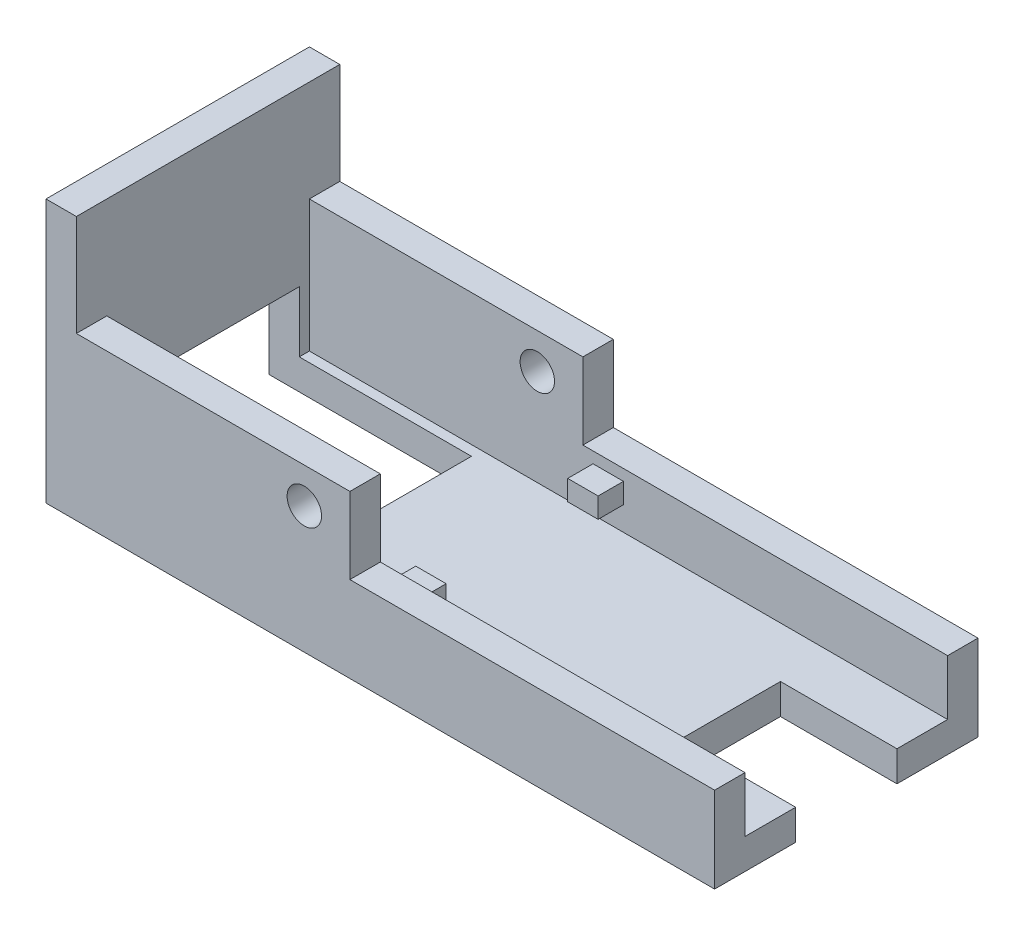
SolidWorks part; units mm, degrees
ref_plane "Front Plane" through (0, 0, 0) normal (0, 0, 1) x (1, 0, 0)
ref_plane "Top Plane" through (0, 0, 0) normal (0, 1, 0) x (1, 0, 0)
ref_plane "Right Plane" through (0, 0, 0) normal (1, 0, 0) x (0, 0, -1)
sketch "Sketch1" plane through (0, 0, 0) normal (0, 1, 0) x (1, 0, 0)
  line L0 (30, 10) -> (33, 10)
  line L1 (-30, -10) -> (30, -10)
  line L2 (-30, -10) -> (-30, 10)
  line L3 (-30, 10) -> (30, 10)
  line L4 (30, -10) -> (30, 10)
  line L5 (-30, -10) -> (30, 10) construction
  line L6 (-30, 10) -> (30, -10) construction
  line L7 (-33, -13) -> (33, -13)
  line L8 (-33, -13) -> (-33, 13)
  line L9 (-33, 13) -> (33, 13)
  line L10 (33, -13) -> (33, 13)
  line L11 (-33, -13) -> (33, 13) construction
  line L12 (-33, 13) -> (33, -13) construction
  line L13 (30, -10) -> (33, -10)
  point P0 (0, 0)
  point P6 (0, 0)
  dimension "D1" = 60
  dimension "D2" = 20
  dimension "D3" = 3
  dimension "D4" = 3
extrude "Boss-Extrude1" add sketch "Sketch1" along normal blind 3 contours L8 L9 L10 L7
extrude "Boss-Extrude2" add sketch "Sketch1<3>" along normal blind 3 from surface contours L13 L1 L2 L3 L0 L10 L9 L8 L7 region at (0, 0, -10.7094) starting at face at (0, 3, 0)
sketch "Sketch1<3>" plane through (0, 0, 0) normal (0, 1, 0) x (1, 0, 0) same geometry as "Sketch1"
sketch "Sketch2" plane through (0, 6, 0) normal (0, 1, 0) x (1, 0, 0)
  line L0 (-3, 13) -> (-3, 10)
  line L1 (-3, -10) -> (-3, -13)
  line L2 (-30, 10) -> (-30, 13)
  line L3 (-30, -10) -> (-30, -13)
  line L8 (33, -13) -> (33, -10)
  line L9 (33, -10) -> (-30, -10)
  line L10 (-30, -10) -> (-30, 10)
  line L11 (-30, 10) -> (33, 10)
  line L12 (33, 10) -> (33, 13)
  line L13 (33, 13) -> (-33, 13)
  line L14 (-33, 13) -> (-33, -13)
  line L15 (-33, -13) -> (33, -13)
  line L16 (33, -13) -> (33, -10)
  line L17 (33, -10) -> (-30, -10)
  line L18 (-30, -10) -> (-30, 10)
  line L19 (-30, 10) -> (33, 10)
  line L20 (33, 10) -> (33, 13)
  line L21 (33, 13) -> (-33, 13)
  line L22 (-33, 13) -> (-33, -13)
  line L23 (-33, -13) -> (33, -13)
  line M11 (33, -13) -> (33, -10)
  line M12 (33, -10) -> (-30, -10)
  line M13 (-30, -10) -> (-30, 10)
  line M14 (-30, 10) -> (33, 10)
  line M15 (33, 10) -> (33, 13)
  line M16 (33, 13) -> (-33, 13)
  line M17 (-33, 13) -> (-33, -13)
  line M18 (-33, -13) -> (33, -13)
  dimension "D2" = 27
  dimension "D1" = 0
extrude "Boss-Extrude3" add sketch "Sketch2" along normal blind 10 contours L1 L0 M12 M13 M14 M16 M17 M18 | L3 L1 M12 M18 | L2 L0 M14 M16 region at (-16.5, 6, -11.5) region at (-31.5, 6, 0) region at (-16.5, 6, 11.5)
extrude "Boss-Extrude4" add sketch "Sketch2<3>" along normal blind 10 from surface contours L3 L2 M13 M16 M17 M18 region at (-31.5, 6, 0) starting at face at (-17.25, 16, 0)
sketch "Sketch2<3>" plane through (0, 6, 0) normal (0, 1, 0) x (1, 0, 0) same geometry as "Sketch2"
extrude "Boss-Extrude5" add sketch "Sketch2<4>" along normal blind 2.46 contours L0 M16 M14 M15 | L1 M12 M18 M11 region at (15, 6, -11.5) region at (15, 6, 11.5)
sketch "Sketch2<4>" plane through (0, 6, 0) normal (0, 1, 0) x (1, 0, 0) same geometry as "Sketch2"
sketch "Sketch3" plane through (0, 0, -10) normal (0, 0, 1) x (1, 0, 0)
  line L0 (-3, 8.46) -> (33, 8.46) construction
  line L1 (-2, 7.36) -> (1, 7.36)
  line L2 (-2, 7.36) -> (-2, 5.36)
  line L3 (-2, 5.36) -> (1, 5.36)
  line L4 (1, 7.36) -> (1, 5.36)
  line L5 (-2, 7.36) -> (1, 5.36) construction
  line L6 (-2, 5.36) -> (1, 7.36) construction
  line L7 (-3, 16) -> (-3, 8.46) construction
  point P0 (-0.5, 6.36)
  dimension "D1" = 3
  dimension "D2" = 2
  dimension "D3" = 1.1
  dimension "D4" = 1
extrude "Boss-Extrude6" add sketch "Sketch3" along normal blind 2.5
mirror "Mirror1" about plane through (0, 0, 0) normal (0, 0, 1) of "Boss-Extrude6"
sketch "Sketch4" plane through (0, 0, 0) normal (0, -1, 0) x (1, 0, 0)
  line L0 (33, 13) -> (33, -13) construction
  line L1 (21.5, -5) -> (33, -5)
  line L2 (21.5, -5) -> (21.5, 5)
  line L3 (21.5, 5) -> (33, 5)
  line L4 (33, -5) -> (33, 5)
  line L5 (21.5, -5) -> (33, 5) construction
  line L6 (21.5, 5) -> (33, -5) construction
  point P0 (27.25, 0)
  dimension "D1" = 10
  dimension "D2" = 11.5
extrude "Cut-Extrude1" cut sketch "Sketch4" against normal through all both and the other way through all
sketch "Sketch5" plane through (0, 0, 13) normal (0, 0, 1) x (1, 0, 0)
  line L0 (-30, 16) -> (-3, 16) construction
  line L1 (-3, 16) -> (-3, 8.46) construction
  point P0 (-7.5, 12.5)
  dimension "D1" = 3.5
  dimension "D2" = 4.5
hole_wizard "M3 Clearance Hole1" positions "Sketch6" profile "Sketch7" hole size "M3" standard "ISO" end condition through all
sketch "Sketch6" plane through (0, 0, 13) normal (0, 0, 1) x (1, 0, 0)
  point P0 (-7.5, 12.5)
sketch "Sketch7" plane through (-7.5, 12.5, 13) normal (1, 0, 0) x (0, -1, 0)
  line L0 (0, 0) -> (0, 26)
  line L1 (0, 26) -> (1.7, 26)
  line L2 (1.7, 26) -> (1.7, 0)
  line L5 (1.7, 0) -> (0, 0)
  line L11 (0, -6.35) -> (0, 107.95) construction
  dimension "Thru Hole Dia." = 3.4
  dimension "Thru Hole Depth" = 26
sketch "Sketch8" plane through (-33, 0, 0) normal (-1, 0, 0) x (0, 0, 1)
  line L0 (13, 0) -> (-13, 0) construction
  line L1 (-9, 9) -> (-9, 0)
  line L2 (9, 9) -> (9, 0)
  line L3 (9, 0) -> (-9, 0)
  line L4 (-9, 9) -> (9, 9)
  line L5 (0, 0) -> (0, 16.1698) construction
  dimension "D1" = 18
  dimension "D2" = 9
extrude "Cut-Extrude2" cut sketch "Sketch8" against normal blind 20
